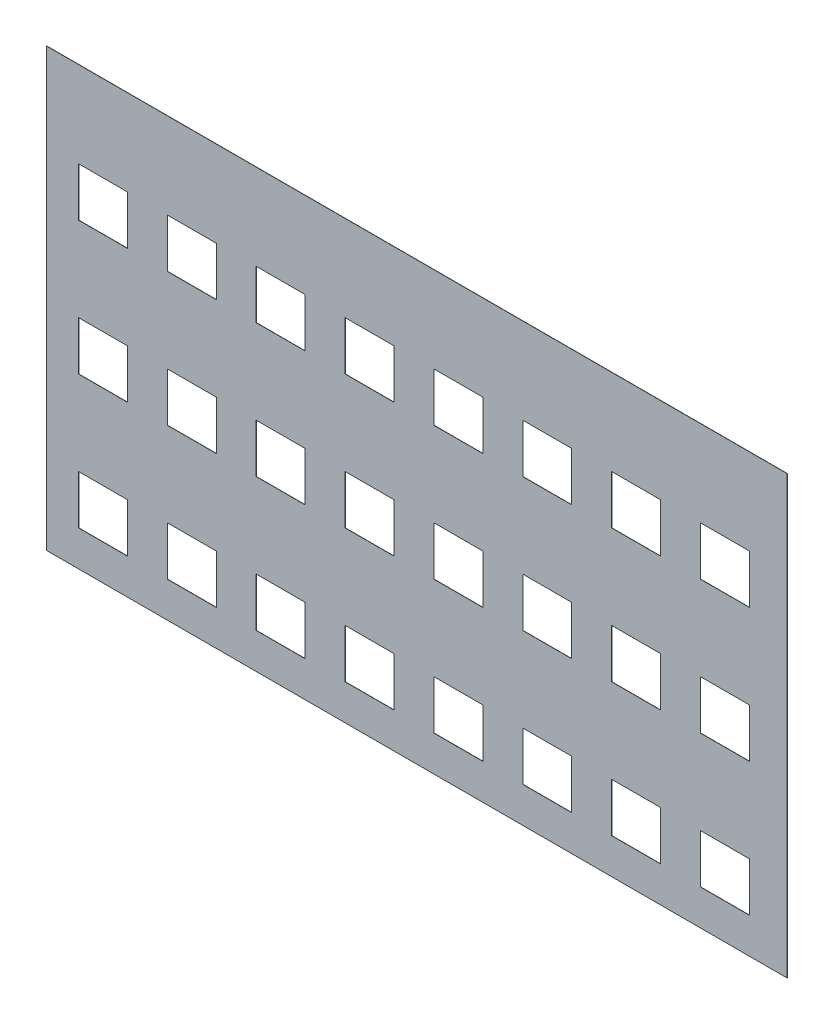
SolidWorks part; units mm, degrees
ref_plane "Front Plane" through (0, 0, 0) normal (0, 0, 1) x (1, 0, 0)
ref_plane "Top Plane" through (0, 0, 0) normal (0, 1, 0) x (1, 0, 0)
ref_plane "Right Plane" through (0, 0, 0) normal (1, 0, 0) x (0, 0, -1)
sketch "Model" plane through (0, 0, 0) normal (0, 0, 1) x (1, 0, 0)
  line L0 (1790, 440) -> (1640, 440)
  line L1 (1640, 440) -> (1640, 595)
  line L2 (1640, 595) -> (1650, 595)
  line L3 (1650, 595) -> (1650, 662)
  line L4 (1650, 662) -> (1780, 662)
  line L5 (1780, 662) -> (1780, 595)
  line L6 (1780, 595) -> (1790, 595)
  line L7 (1790, 595) -> (1790, 440)
  line L8 (1595, 440) -> (1445, 440)
  line L9 (1445, 440) -> (1445, 595)
  line L10 (1445, 595) -> (1455, 595)
  line L11 (1455, 595) -> (1455, 662)
  line L12 (1455, 662) -> (1585, 662)
  line L13 (1585, 662) -> (1585, 595)
  line L14 (1585, 595) -> (1595, 595)
  line L15 (1595, 595) -> (1595, 440)
  line L16 (1400, 440) -> (1250, 440)
  line L17 (1250, 440) -> (1250, 595)
  line L18 (1250, 595) -> (1260, 595)
  line L19 (1260, 595) -> (1260, 662)
  line L20 (1260, 662) -> (1390, 662)
  line L21 (1390, 662) -> (1390, 595)
  line L22 (1390, 595) -> (1400, 595)
  line L23 (1400, 595) -> (1400, 440)
  line L24 (1205, 440) -> (1055, 440)
  line L25 (1055, 440) -> (1055, 595)
  line L26 (1055, 595) -> (1065, 595)
  line L27 (1065, 595) -> (1065, 662)
  line L28 (1065, 662) -> (1195, 662)
  line L29 (1195, 662) -> (1195, 595)
  line L30 (1195, 595) -> (1205, 595)
  line L31 (1205, 595) -> (1205, 440)
  line L32 (1010, 440) -> (860, 440)
  line L33 (860, 440) -> (860, 595)
  line L34 (860, 595) -> (870, 595)
  line L35 (870, 595) -> (870, 662)
  line L36 (870, 662) -> (1000, 662)
  line L37 (1000, 662) -> (1000, 595)
  line L38 (1000, 595) -> (1010, 595)
  line L39 (1010, 595) -> (1010, 440)
  line L40 (815, 440) -> (665, 440)
  line L41 (665, 440) -> (665, 595)
  line L42 (665, 595) -> (675, 595)
  line L43 (675, 595) -> (675, 662)
  line L44 (675, 662) -> (805, 662)
  line L45 (805, 662) -> (805, 595)
  line L46 (805, 595) -> (815, 595)
  line L47 (815, 595) -> (815, 440)
  line L48 (620, 440) -> (470, 440)
  line L49 (470, 440) -> (470, 595)
  line L50 (470, 595) -> (480, 595)
  line L51 (480, 595) -> (480, 662)
  line L52 (480, 662) -> (610, 662)
  line L53 (610, 662) -> (610, 595)
  line L54 (610, 595) -> (620, 595)
  line L55 (620, 595) -> (620, 440)
  line L56 (425, 440) -> (275, 440)
  line L57 (275, 440) -> (275, 595)
  line L58 (275, 595) -> (285, 595)
  line L59 (285, 595) -> (285, 662)
  line L60 (285, 662) -> (415, 662)
  line L61 (415, 662) -> (415, 595)
  line L62 (415, 595) -> (425, 595)
  line L63 (425, 595) -> (425, 440)
  line L64 (230, 440) -> (80, 440)
  line L65 (80, 440) -> (80, 595)
  line L66 (80, 595) -> (90, 595)
  line L67 (90, 595) -> (90, 662)
  line L68 (90, 662) -> (220, 662)
  line L69 (220, 662) -> (220, 595)
  line L70 (220, 595) -> (230, 595)
  line L71 (230, 595) -> (230, 440)
  line L72 (1790, 805) -> (1640, 805)
  line L73 (1640, 805) -> (1640, 960)
  line L74 (1640, 960) -> (1650, 960)
  line L75 (1650, 960) -> (1650, 1027)
  line L76 (1650, 1027) -> (1780, 1027)
  line L77 (1780, 1027) -> (1780, 960)
  line L78 (1780, 960) -> (1790, 960)
  line L79 (1790, 960) -> (1790, 805)
  line L80 (1595, 805) -> (1445, 805)
  line L81 (1445, 805) -> (1445, 960)
  line L82 (1445, 960) -> (1455, 960)
  line L83 (1455, 960) -> (1455, 1027)
  line L84 (1455, 1027) -> (1585, 1027)
  line L85 (1585, 1027) -> (1585, 960)
  line L86 (1585, 960) -> (1595, 960)
  line L87 (1595, 960) -> (1595, 805)
  line L88 (1400, 805) -> (1250, 805)
  line L89 (1250, 805) -> (1250, 960)
  line L90 (1250, 960) -> (1260, 960)
  line L91 (1260, 960) -> (1260, 1027)
  line L92 (1260, 1027) -> (1390, 1027)
  line L93 (1390, 1027) -> (1390, 960)
  line L94 (1390, 960) -> (1400, 960)
  line L95 (1400, 960) -> (1400, 805)
  line L96 (1205, 805) -> (1055, 805)
  line L97 (1055, 805) -> (1055, 960)
  line L98 (1055, 960) -> (1065, 960)
  line L99 (1065, 960) -> (1065, 1027)
  line L100 (1065, 1027) -> (1195, 1027)
  line L101 (1195, 1027) -> (1195, 960)
  line L102 (1195, 960) -> (1205, 960)
  line L103 (1205, 960) -> (1205, 805)
  line L104 (1010, 805) -> (860, 805)
  line L105 (860, 805) -> (860, 960)
  line L106 (860, 960) -> (870, 960)
  line L107 (870, 960) -> (870, 1027)
  line L108 (870, 1027) -> (1000, 1027)
  line L109 (1000, 1027) -> (1000, 960)
  line L110 (1000, 960) -> (1010, 960)
  line L111 (1010, 960) -> (1010, 805)
  line L112 (815, 805) -> (665, 805)
  line L113 (665, 805) -> (665, 960)
  line L114 (665, 960) -> (675, 960)
  line L115 (675, 960) -> (675, 1027)
  line L116 (675, 1027) -> (805, 1027)
  line L117 (805, 1027) -> (805, 960)
  line L118 (805, 960) -> (815, 960)
  line L119 (815, 960) -> (815, 805)
  line L120 (620, 805) -> (470, 805)
  line L121 (470, 805) -> (470, 960)
  line L122 (470, 960) -> (480, 960)
  line L123 (480, 960) -> (480, 1027)
  line L124 (480, 1027) -> (610, 1027)
  line L125 (610, 1027) -> (610, 960)
  line L126 (610, 960) -> (620, 960)
  line L127 (620, 960) -> (620, 805)
  line L128 (425, 805) -> (275, 805)
  line L129 (275, 805) -> (275, 960)
  line L130 (275, 960) -> (285, 960)
  line L131 (285, 960) -> (285, 1027)
  line L132 (285, 1027) -> (415, 1027)
  line L133 (415, 1027) -> (415, 960)
  line L134 (415, 960) -> (425, 960)
  line L135 (425, 960) -> (425, 805)
  line L136 (230, 805) -> (80, 805)
  line L137 (80, 805) -> (80, 960)
  line L138 (80, 960) -> (90, 960)
  line L139 (90, 960) -> (90, 1027)
  line L140 (90, 1027) -> (220, 1027)
  line L141 (220, 1027) -> (220, 960)
  line L142 (220, 960) -> (230, 960)
  line L143 (230, 960) -> (230, 805)
  line L144 (1790, 75) -> (1640, 75)
  line L145 (1640, 75) -> (1640, 230)
  line L146 (1640, 230) -> (1650, 230)
  line L147 (1650, 230) -> (1650, 297)
  line L148 (1650, 297) -> (1780, 297)
  line L149 (1780, 297) -> (1780, 230)
  line L150 (1780, 230) -> (1790, 230)
  line L151 (1790, 230) -> (1790, 75)
  line L152 (1595, 75) -> (1445, 75)
  line L153 (1445, 75) -> (1445, 230)
  line L154 (1445, 230) -> (1455, 230)
  line L155 (1455, 230) -> (1455, 297)
  line L156 (1455, 297) -> (1585, 297)
  line L157 (1585, 297) -> (1585, 230)
  line L158 (1585, 230) -> (1595, 230)
  line L159 (1595, 230) -> (1595, 75)
  line L160 (1400, 75) -> (1250, 75)
  line L161 (1250, 75) -> (1250, 230)
  line L162 (1250, 230) -> (1260, 230)
  line L163 (1260, 230) -> (1260, 297)
  line L164 (1260, 297) -> (1390, 297)
  line L165 (1390, 297) -> (1390, 230)
  line L166 (1390, 230) -> (1400, 230)
  line L167 (1400, 230) -> (1400, 75)
  line L168 (1205, 75) -> (1055, 75)
  line L169 (1055, 75) -> (1055, 230)
  line L170 (1055, 230) -> (1065, 230)
  line L171 (1065, 230) -> (1065, 297)
  line L172 (1065, 297) -> (1195, 297)
  line L173 (1195, 297) -> (1195, 230)
  line L174 (1195, 230) -> (1205, 230)
  line L175 (1205, 230) -> (1205, 75)
  line L176 (1010, 75) -> (860, 75)
  line L177 (860, 75) -> (860, 230)
  line L178 (860, 230) -> (870, 230)
  line L179 (870, 230) -> (870, 297)
  line L180 (870, 297) -> (1000, 297)
  line L181 (1000, 297) -> (1000, 230)
  line L182 (1000, 230) -> (1010, 230)
  line L183 (1010, 230) -> (1010, 75)
  line L184 (815, 75) -> (665, 75)
  line L185 (665, 75) -> (665, 230)
  line L186 (665, 230) -> (675, 230)
  line L187 (675, 230) -> (675, 297)
  line L188 (675, 297) -> (805, 297)
  line L189 (805, 297) -> (805, 230)
  line L190 (805, 230) -> (815, 230)
  line L191 (815, 230) -> (815, 75)
  line L192 (620, 75) -> (470, 75)
  line L193 (470, 75) -> (470, 230)
  line L194 (470, 230) -> (480, 230)
  line L195 (480, 230) -> (480, 297)
  line L196 (480, 297) -> (610, 297)
  line L197 (610, 297) -> (610, 230)
  line L198 (610, 230) -> (620, 230)
  line L199 (620, 230) -> (620, 75)
  line L200 (425, 75) -> (275, 75)
  line L201 (275, 75) -> (275, 230)
  line L202 (275, 230) -> (285, 230)
  line L203 (285, 230) -> (285, 297)
  line L204 (285, 297) -> (415, 297)
  line L205 (415, 297) -> (415, 230)
  line L206 (415, 230) -> (425, 230)
  line L207 (425, 230) -> (425, 75)
  line L208 (230, 75) -> (80, 75)
  line L209 (80, 75) -> (80, 230)
  line L210 (80, 230) -> (90, 230)
  line L211 (90, 230) -> (90, 297)
  line L212 (90, 297) -> (220, 297)
  line L213 (220, 297) -> (220, 230)
  line L214 (220, 230) -> (230, 230)
  line L215 (230, 230) -> (230, 75)
  line L216 (0, 1180) -> (0, 0)
  line L217 (0, 0) -> (1870, 0)
  line L218 (1870, 0) -> (1870, 1180)
  line L219 (1870, 1180) -> (0, 1180)
  dimension "D1" = 3
base flange "Base-Flange1" sketch "Model" thickness 0.6 reverse thickness direction no parameters "D1"=0.7366
sketch "Sketch6" plane through (0, 0, 0) normal (0, 0, 1) x (1, 0, 0)
  line L3 (1705, 805) -> (1725, 805)
  line L7 (1725, 1027) -> (1705, 1027)
  line L8 (1779, 1026) -> (1725, 1026)
  line L9 (1651, 1026) -> (1651, 959)
  line L10 (1651, 959) -> (1641, 959)
  line L11 (1641, 959) -> (1641, 806)
  line L12 (1641, 806) -> (1705, 806)
  line L13 (1789, 806) -> (1789, 959)
  line L14 (1789, 959) -> (1779, 959)
  line L15 (1779, 959) -> (1779, 1026)
  line L16 (1705, 1026) -> (1651, 1026)
  line L17 (1780, 1027) -> (1650, 1027) construction
  line L18 (1705, 1027) -> (1705, 1026)
  line L19 (1725, 1027) -> (1725, 1026)
  line L20 (1705, 806) -> (1705, 805)
  line L21 (1725, 806) -> (1725, 805)
  line L22 (1725, 806) -> (1789, 806)
  line L23 (1641, 806) -> (1789, 806) construction
  line L24 (1779, 1026) -> (1651, 1026) construction
  line L25 (1640, 805) -> (1790, 805) construction
  line L26 (1650, 1027) -> (1650, 960) construction
  line L27 (1650, 960) -> (1640, 960) construction
  line L28 (1640, 960) -> (1640, 805) construction
  line L29 (1790, 805) -> (1790, 960) construction
  line L30 (1790, 960) -> (1780, 960) construction
  line L31 (1780, 960) -> (1780, 1027) construction
  line L32 (1705, 440) -> (1725, 440)
  line L33 (1725, 662) -> (1705, 662)
  line L34 (1779, 661) -> (1725, 661)
  line L35 (1651, 661) -> (1651, 594)
  line L36 (1651, 594) -> (1641, 594)
  line L37 (1641, 594) -> (1641, 441)
  line L38 (1641, 441) -> (1705, 441)
  line L39 (1789, 441) -> (1789, 594)
  line L40 (1789, 594) -> (1779, 594)
  line L41 (1779, 594) -> (1779, 661)
  line L42 (1705, 661) -> (1651, 661)
  line L43 (1705, 662) -> (1705, 661)
  line L44 (1725, 662) -> (1725, 661)
  line L45 (1705, 441) -> (1705, 440)
  line L46 (1725, 441) -> (1725, 440)
  line L47 (1725, 441) -> (1789, 441)
  line L48 (1705, 75) -> (1725, 75)
  line L49 (1725, 297) -> (1705, 297)
  line L50 (1779, 296) -> (1725, 296)
  line L51 (1651, 296) -> (1651, 229)
  line L52 (1651, 229) -> (1641, 229)
  line L53 (1641, 229) -> (1641, 76)
  line L54 (1641, 76) -> (1705, 76)
  line L55 (1789, 76) -> (1789, 229)
  line L56 (1789, 229) -> (1779, 229)
  line L57 (1779, 229) -> (1779, 296)
  line L58 (1705, 296) -> (1651, 296)
  line L59 (1705, 297) -> (1705, 296)
  line L60 (1725, 297) -> (1725, 296)
  line L61 (1705, 76) -> (1705, 75)
  line L62 (1725, 76) -> (1725, 75)
  line L63 (1725, 76) -> (1789, 76)
  dimension "D1" = 1
  dimension "D2" = 3
base flange "Tab1" sketch "Sketch6" thickness 0.6 reverse thickness direction no parameters "D1"=0.7366
sketch "Sketch7" plane through (0, 0, 0) normal (0, 0, 1) x (1, 0, 0)
  line L1 (1870, 1180) -> (1935, 1180)
  line L2 (1870, 1180) -> (1870, 0)
  line L3 (1870, 0) -> (1935, 0)
  line L4 (1935, 1180) -> (1935, 0)
  line L5 (0, 0) -> (-65, 0)
  line L6 (0, 0) -> (0, 1180)
  line L7 (0, 1180) -> (-65, 1180)
  line L8 (-65, 0) -> (-65, 1180)
  dimension "D1" = 65
  dimension "D2" = 65
base flange "Tab2" sketch "Sketch7" thickness 0.6 reverse thickness direction no parameters "D1"=0.7366
sketch "Sketch9" plane through (0, 0, 0) normal (0, 0, 1) x (1, 0, 0)
  line L1 (30.4802, 1078.5447) -> (1870.8092, 1078.5447)
  line L2 (30.4802, 1078.5447) -> (30.4802, 32.6023)
  line L3 (30.4802, 32.6023) -> (1870.8092, 32.6023)
  line L4 (1870.8092, 1078.5447) -> (1870.8092, 32.6023)
extrude "Boss-Extrude1" add sketch "Sketch9" against normal up to surface (0.6 mm away)
sketch "Sketch8" plane through (0, 0, 0) normal (0, 0, 1) x (1, 0, 0)
  line L84 (1701.0507, 947.9116) -> (1701.0507, 815.9116)
  line L85 (1833.0507, 947.9116) -> (1701.0507, 947.9116)
  line L86 (1833.0507, 815.9116) -> (1833.0507, 947.9116)
  line L87 (1701.0507, 815.9116) -> (1833.0507, 815.9116)
  line L288 (1461.0507, 947.9116) -> (1461.0507, 815.9116)
  line L289 (1461.0507, 815.9116) -> (1593.0507, 815.9116)
  line L290 (1593.0507, 815.9116) -> (1593.0507, 947.9116)
  line L291 (1593.0507, 947.9116) -> (1461.0507, 947.9116)
  line L292 (1221.0507, 947.9116) -> (1221.0507, 815.9116)
  line L293 (1221.0507, 815.9116) -> (1353.0507, 815.9116)
  line L294 (1353.0507, 815.9116) -> (1353.0507, 947.9116)
  line L295 (1353.0507, 947.9116) -> (1221.0507, 947.9116)
  line L296 (981.0507, 947.9116) -> (981.0507, 815.9116)
  line L297 (981.0507, 815.9116) -> (1113.0507, 815.9116)
  line L298 (1113.0507, 815.9116) -> (1113.0507, 947.9116)
  line L299 (1113.0507, 947.9116) -> (981.0507, 947.9116)
  line L300 (741.0507, 947.9116) -> (741.0507, 815.9116)
  line L301 (741.0507, 815.9116) -> (873.0507, 815.9116)
  line L302 (873.0507, 815.9116) -> (873.0507, 947.9116)
  line L303 (873.0507, 947.9116) -> (741.0507, 947.9116)
  line L304 (501.0507, 947.9116) -> (501.0507, 815.9116)
  line L305 (501.0507, 815.9116) -> (633.0507, 815.9116)
  line L306 (633.0507, 815.9116) -> (633.0507, 947.9116)
  line L307 (633.0507, 947.9116) -> (501.0507, 947.9116)
  line L308 (261.0507, 947.9116) -> (261.0507, 815.9116)
  line L309 (261.0507, 815.9116) -> (393.0507, 815.9116)
  line L310 (393.0507, 815.9116) -> (393.0507, 947.9116)
  line L311 (393.0507, 947.9116) -> (261.0507, 947.9116)
  line L312 (21.0507, 947.9116) -> (21.0507, 815.9116)
  line L313 (21.0507, 815.9116) -> (153.0507, 815.9116)
  line L314 (153.0507, 815.9116) -> (153.0507, 947.9116)
  line L315 (153.0507, 947.9116) -> (21.0507, 947.9116)
  line L316 (1461.0507, 587.9116) -> (1461.0507, 455.9116)
  line L317 (1461.0507, 455.9116) -> (1593.0507, 455.9116)
  line L318 (1593.0507, 455.9116) -> (1593.0507, 587.9116)
  line L319 (1593.0507, 587.9116) -> (1461.0507, 587.9116)
  line L320 (1221.0507, 587.9116) -> (1221.0507, 455.9116)
  line L321 (1221.0507, 455.9116) -> (1353.0507, 455.9116)
  line L322 (1353.0507, 455.9116) -> (1353.0507, 587.9116)
  line L323 (1353.0507, 587.9116) -> (1221.0507, 587.9116)
  line L324 (981.0507, 587.9116) -> (981.0507, 455.9116)
  line L325 (981.0507, 455.9116) -> (1113.0507, 455.9116)
  line L326 (1113.0507, 455.9116) -> (1113.0507, 587.9116)
  line L327 (1113.0507, 587.9116) -> (981.0507, 587.9116)
  line L328 (741.0507, 587.9116) -> (741.0507, 455.9116)
  line L329 (741.0507, 455.9116) -> (873.0507, 455.9116)
  line L330 (873.0507, 455.9116) -> (873.0507, 587.9116)
  line L331 (873.0507, 587.9116) -> (741.0507, 587.9116)
  line L332 (501.0507, 587.9116) -> (501.0507, 455.9116)
  line L333 (501.0507, 455.9116) -> (633.0507, 455.9116)
  line L334 (633.0507, 455.9116) -> (633.0507, 587.9116)
  line L335 (633.0507, 587.9116) -> (501.0507, 587.9116)
  line L336 (261.0507, 587.9116) -> (261.0507, 455.9116)
  line L337 (261.0507, 455.9116) -> (393.0507, 455.9116)
  line L338 (393.0507, 455.9116) -> (393.0507, 587.9116)
  line L339 (393.0507, 587.9116) -> (261.0507, 587.9116)
  line L340 (21.0507, 587.9116) -> (21.0507, 455.9116)
  line L341 (21.0507, 455.9116) -> (153.0507, 455.9116)
  line L342 (153.0507, 455.9116) -> (153.0507, 587.9116)
  line L343 (153.0507, 587.9116) -> (21.0507, 587.9116)
  line L344 (1461.0507, 227.9116) -> (1461.0507, 95.9116)
  line L345 (1461.0507, 95.9116) -> (1593.0507, 95.9116)
  line L346 (1593.0507, 95.9116) -> (1593.0507, 227.9116)
  line L347 (1593.0507, 227.9116) -> (1461.0507, 227.9116)
  line L348 (1221.0507, 227.9116) -> (1221.0507, 95.9116)
  line L349 (1221.0507, 95.9116) -> (1353.0507, 95.9116)
  line L350 (1353.0507, 95.9116) -> (1353.0507, 227.9116)
  line L351 (1353.0507, 227.9116) -> (1221.0507, 227.9116)
  line L352 (981.0507, 227.9116) -> (981.0507, 95.9116)
  line L353 (981.0507, 95.9116) -> (1113.0507, 95.9116)
  line L354 (1113.0507, 95.9116) -> (1113.0507, 227.9116)
  line L355 (1113.0507, 227.9116) -> (981.0507, 227.9116)
  line L356 (741.0507, 227.9116) -> (741.0507, 95.9116)
  line L357 (741.0507, 95.9116) -> (873.0507, 95.9116)
  line L358 (873.0507, 95.9116) -> (873.0507, 227.9116)
  line L359 (873.0507, 227.9116) -> (741.0507, 227.9116)
  line L360 (501.0507, 227.9116) -> (501.0507, 95.9116)
  line L361 (501.0507, 95.9116) -> (633.0507, 95.9116)
  line L362 (633.0507, 95.9116) -> (633.0507, 227.9116)
  line L363 (633.0507, 227.9116) -> (501.0507, 227.9116)
  line L364 (261.0507, 227.9116) -> (261.0507, 95.9116)
  line L365 (261.0507, 95.9116) -> (393.0507, 95.9116)
  line L366 (393.0507, 95.9116) -> (393.0507, 227.9116)
  line L367 (393.0507, 227.9116) -> (261.0507, 227.9116)
  line L368 (21.0507, 227.9116) -> (21.0507, 95.9116)
  line L369 (21.0507, 95.9116) -> (153.0507, 95.9116)
  line L370 (153.0507, 95.9116) -> (153.0507, 227.9116)
  line L371 (153.0507, 227.9116) -> (21.0507, 227.9116)
  line L372 (1701.0507, 587.9116) -> (1701.0507, 455.9116)
  line L373 (1701.0507, 455.9116) -> (1833.0507, 455.9116)
  line L374 (1833.0507, 455.9116) -> (1833.0507, 587.9116)
  line L375 (1833.0507, 587.9116) -> (1701.0507, 587.9116)
  line L376 (1701.0507, 227.9116) -> (1701.0507, 95.9116)
  line L377 (1701.0507, 95.9116) -> (1833.0507, 95.9116)
  line L378 (1833.0507, 95.9116) -> (1833.0507, 227.9116)
  line L379 (1833.0507, 227.9116) -> (1701.0507, 227.9116)
  dimension "D1" = 3
extrude "Cut-Extrude1" cut sketch "Sketch8" against normal blind 10 normal cut yes
sketch "Bend-Lines1" [suppressed] plane through (0, 0, 0) normal (0, 1, 0) x (1, 0, 0)
sketch "Bounding-Box1" [suppressed] plane through (0, 0, 0) normal (0, 1, 0) x (1, 0, 0)
sheet metal parameters "Sheet-Metal1" thickness 0.6 parameters "D1"=0.7366
flat pattern "Flat-Pattern1" [suppressed]
sketch "Bend-Lines2" plane through (0, 0, 0) normal (0, 1, 0) x (1, 0, 0)
sketch3d "Bounding-Box2" [suppressed]
  line L0 (0, 0, 0) -> (-1870, 0, 0) construction
  line L1 (0, 1180, 0) -> (-1870, 1180, 0) construction
  line L2 (0, 0, 0) -> (0, 1180, 0) construction
  line L3 (-1870, 0, 0) -> (-1870, 1180, 0) construction
sheet metal parameters "Sheet-Metal2" thickness 0.6 parameters "D1"=0.7366
flat pattern "Flat-Pattern2"
sketch "Bend-Lines3" plane through (0, 0, 0) normal (0, 1, 0) x (1, 0, 0)
sketch3d "Bounding-Box3" [suppressed]
  line L0 (0, 0, 0) -> (-1870, 0, 0) construction
  line L1 (0, 1180, 0) -> (-1870, 1180, 0) construction
  line L2 (0, 0, 0) -> (0, 1180, 0) construction
  line L3 (-1870, 0, 0) -> (-1870, 1180, 0) construction
sheet metal parameters "Sheet-Metal5" thickness 0.6 parameters "D1"=0.7366
flat pattern "Flat-Pattern5"
sketch "Bend-Lines4" plane through (0, 0, 0) normal (0, 1, 0) x (1, 0, 0)
sketch3d "Bounding-Box4" [suppressed]
  line L0 (65, 0, 0) -> (-1935, 0, 0) construction
  line L1 (65, 1180, 0) -> (-1935, 1180, 0) construction
  line L2 (65, 0, 0) -> (65, 1180, 0) construction
  line L3 (-1935, 0, 0) -> (-1935, 1180, 0) construction
sheet metal parameters "Sheet-Metal6" thickness 0.6 parameters "D1"=0.7366
flat pattern "Flat-Pattern5" [suppressed]
sketch "Bend-Lines4" plane through (0, 0, 0) normal (0, 1, 0) x (1, 0, 0)
sketch3d "Bounding-Box4" [suppressed]
  line L0 (65, 0, 0) -> (-1935, 0, 0) construction
  line L1 (65, 1180, 0) -> (-1935, 1180, 0) construction
  line L2 (65, 0, 0) -> (65, 1180, 0) construction
  line L3 (-1935, 0, 0) -> (-1935, 1180, 0) construction
sketch "Sketch8-1" plane through (0, 0, 0) normal (0, 0, 1) x (1, 0, 0)
  line L0 (91.0507, 947.9116) -> (91.0507, 815.9116)
  line L1 (223.0507, 947.9116) -> (91.0507, 947.9116)
  line L2 (223.0507, 815.9116) -> (223.0507, 947.9116)
  line L3 (91.0507, 815.9116) -> (223.0507, 815.9116)
  line L4 (67.0507, 1045.9116) -> (82.0507, 1045.9116)
  line L5 (232.0507, 1045.9116) -> (82.0507, 1045.9116)
  line L6 (247.0507, 1045.9116) -> (232.0507, 1045.9116)
  line L7 (247.0507, 968.9116) -> (247.0507, 1045.9116)
  line L8 (247.0507, 793.9116) -> (247.0507, 968.9116)
  line L9 (67.0507, 793.9116) -> (247.0507, 793.9116)
  line L10 (67.0507, 973.9116) -> (67.0507, 793.9116)
  line L11 (67.0507, 973.9116) -> (67.0507, 1045.9116)
  line L12 (321.0507, 947.9116) -> (321.0507, 815.9116)
  line L13 (453.0507, 947.9116) -> (321.0507, 947.9116)
  line L14 (453.0507, 815.9116) -> (453.0507, 947.9116)
  line L15 (321.0507, 815.9116) -> (453.0507, 815.9116)
  line L16 (297.0507, 1045.9116) -> (312.0507, 1045.9116)
  line L17 (462.0507, 1045.9116) -> (312.0507, 1045.9116)
  line L18 (477.0507, 1045.9116) -> (462.0507, 1045.9116)
  line L19 (477.0507, 968.9116) -> (477.0507, 1045.9116)
  line L20 (477.0507, 793.9116) -> (477.0507, 968.9116)
  line L21 (297.0507, 793.9116) -> (477.0507, 793.9116)
  line L22 (297.0507, 973.9116) -> (297.0507, 793.9116)
  line L23 (297.0507, 973.9116) -> (297.0507, 1045.9116)
  line L24 (551.0507, 947.9116) -> (551.0507, 815.9116)
  line L25 (683.0507, 947.9116) -> (551.0507, 947.9116)
  line L26 (683.0507, 815.9116) -> (683.0507, 947.9116)
  line L27 (551.0507, 815.9116) -> (683.0507, 815.9116)
  line L28 (527.0507, 1045.9116) -> (542.0507, 1045.9116)
  line L29 (692.0507, 1045.9116) -> (542.0507, 1045.9116)
  line L30 (707.0507, 1045.9116) -> (692.0507, 1045.9116)
  line L31 (707.0507, 968.9116) -> (707.0507, 1045.9116)
  line L32 (707.0507, 793.9116) -> (707.0507, 968.9116)
  line L33 (527.0507, 793.9116) -> (707.0507, 793.9116)
  line L34 (527.0507, 973.9116) -> (527.0507, 793.9116)
  line L35 (527.0507, 973.9116) -> (527.0507, 1045.9116)
  line L36 (781.0507, 947.9116) -> (781.0507, 815.9116)
  line L37 (913.0507, 947.9116) -> (781.0507, 947.9116)
  line L38 (913.0507, 815.9116) -> (913.0507, 947.9116)
  line L39 (781.0507, 815.9116) -> (913.0507, 815.9116)
  line L40 (757.0507, 1045.9116) -> (772.0507, 1045.9116)
  line L41 (922.0507, 1045.9116) -> (772.0507, 1045.9116)
  line L42 (937.0507, 1045.9116) -> (922.0507, 1045.9116)
  line L43 (937.0507, 968.9116) -> (937.0507, 1045.9116)
  line L44 (937.0507, 793.9116) -> (937.0507, 968.9116)
  line L45 (757.0507, 793.9116) -> (937.0507, 793.9116)
  line L46 (757.0507, 973.9116) -> (757.0507, 793.9116)
  line L47 (757.0507, 973.9116) -> (757.0507, 1045.9116)
  line L48 (1011.0507, 947.9116) -> (1011.0507, 815.9116)
  line L49 (1143.0507, 947.9116) -> (1011.0507, 947.9116)
  line L50 (1143.0507, 815.9116) -> (1143.0507, 947.9116)
  line L51 (1011.0507, 815.9116) -> (1143.0507, 815.9116)
  line L52 (987.0507, 1045.9116) -> (1002.0507, 1045.9116)
  line L53 (1152.0507, 1045.9116) -> (1002.0507, 1045.9116)
  line L54 (1167.0507, 1045.9116) -> (1152.0507, 1045.9116)
  line L55 (1167.0507, 968.9116) -> (1167.0507, 1045.9116)
  line L56 (1167.0507, 793.9116) -> (1167.0507, 968.9116)
  line L57 (987.0507, 793.9116) -> (1167.0507, 793.9116)
  line L58 (987.0507, 973.9116) -> (987.0507, 793.9116)
  line L59 (987.0507, 973.9116) -> (987.0507, 1045.9116)
  line L60 (1241.0507, 947.9116) -> (1241.0507, 815.9116)
  line L61 (1373.0507, 947.9116) -> (1241.0507, 947.9116)
  line L62 (1373.0507, 815.9116) -> (1373.0507, 947.9116)
  line L63 (1241.0507, 815.9116) -> (1373.0507, 815.9116)
  line L64 (1217.0507, 1045.9116) -> (1232.0507, 1045.9116)
  line L65 (1382.0507, 1045.9116) -> (1232.0507, 1045.9116)
  line L66 (1397.0507, 1045.9116) -> (1382.0507, 1045.9116)
  line L67 (1397.0507, 968.9116) -> (1397.0507, 1045.9116)
  line L68 (1397.0507, 793.9116) -> (1397.0507, 968.9116)
  line L69 (1217.0507, 793.9116) -> (1397.0507, 793.9116)
  line L70 (1217.0507, 973.9116) -> (1217.0507, 793.9116)
  line L71 (1217.0507, 973.9116) -> (1217.0507, 1045.9116)
  line L72 (1471.0507, 947.9116) -> (1471.0507, 815.9116)
  line L73 (1603.0507, 947.9116) -> (1471.0507, 947.9116)
  line L74 (1603.0507, 815.9116) -> (1603.0507, 947.9116)
  line L75 (1471.0507, 815.9116) -> (1603.0507, 815.9116)
  line L76 (1447.0507, 1045.9116) -> (1462.0507, 1045.9116)
  line L77 (1612.0507, 1045.9116) -> (1462.0507, 1045.9116)
  line L78 (1627.0507, 1045.9116) -> (1612.0507, 1045.9116)
  line L79 (1627.0507, 968.9116) -> (1627.0507, 1045.9116)
  line L80 (1627.0507, 793.9116) -> (1627.0507, 968.9116)
  line L81 (1447.0507, 793.9116) -> (1627.0507, 793.9116)
  line L82 (1447.0507, 973.9116) -> (1447.0507, 793.9116)
  line L83 (1447.0507, 973.9116) -> (1447.0507, 1045.9116)
  line L84 (1701.0507, 947.9116) -> (1701.0507, 815.9116)
  line L85 (1833.0507, 947.9116) -> (1701.0507, 947.9116)
  line L86 (1833.0507, 815.9116) -> (1833.0507, 947.9116)
  line L87 (1701.0507, 815.9116) -> (1833.0507, 815.9116)
  line L88 (1677.0507, 1045.9116) -> (1692.0507, 1045.9116)
  line L89 (1842.0507, 1045.9116) -> (1692.0507, 1045.9116)
  line L90 (1857.0507, 1045.9116) -> (1842.0507, 1045.9116)
  line L91 (1857.0507, 968.9116) -> (1857.0507, 1045.9116)
  line L92 (1857.0507, 793.9116) -> (1857.0507, 968.9116)
  line L93 (1677.0507, 793.9116) -> (1857.0507, 793.9116)
  line L94 (1677.0507, 973.9116) -> (1677.0507, 793.9116)
  line L95 (1677.0507, 973.9116) -> (1677.0507, 1045.9116)
  line L96 (91.0507, 587.9116) -> (91.0507, 455.9116)
  line L97 (223.0507, 587.9116) -> (91.0507, 587.9116)
  line L98 (223.0507, 455.9116) -> (223.0507, 587.9116)
  line L99 (91.0507, 455.9116) -> (223.0507, 455.9116)
  line L100 (67.0507, 685.9116) -> (82.0507, 685.9116)
  line L101 (232.0507, 685.9116) -> (82.0507, 685.9116)
  line L102 (247.0507, 685.9116) -> (232.0507, 685.9116)
  line L103 (247.0507, 608.9116) -> (247.0507, 685.9116)
  line L104 (247.0507, 433.9116) -> (247.0507, 608.9116)
  line L105 (67.0507, 433.9116) -> (247.0507, 433.9116)
  line L106 (67.0507, 613.9116) -> (67.0507, 433.9116)
  line L107 (67.0507, 613.9116) -> (67.0507, 685.9116)
  line L108 (321.0507, 587.9116) -> (321.0507, 455.9116)
  line L109 (453.0507, 587.9116) -> (321.0507, 587.9116)
  line L110 (453.0507, 455.9116) -> (453.0507, 587.9116)
  line L111 (321.0507, 455.9116) -> (453.0507, 455.9116)
  line L112 (297.0507, 685.9116) -> (312.0507, 685.9116)
  line L113 (462.0507, 685.9116) -> (312.0507, 685.9116)
  line L114 (477.0507, 685.9116) -> (462.0507, 685.9116)
  line L115 (477.0507, 608.9116) -> (477.0507, 685.9116)
  line L116 (477.0507, 433.9116) -> (477.0507, 608.9116)
  line L117 (297.0507, 433.9116) -> (477.0507, 433.9116)
  line L118 (297.0507, 613.9116) -> (297.0507, 433.9116)
  line L119 (297.0507, 613.9116) -> (297.0507, 685.9116)
  line L120 (551.0507, 587.9116) -> (551.0507, 455.9116)
  line L121 (683.0507, 587.9116) -> (551.0507, 587.9116)
  line L122 (683.0507, 455.9116) -> (683.0507, 587.9116)
  line L123 (551.0507, 455.9116) -> (683.0507, 455.9116)
  line L124 (527.0507, 685.9116) -> (542.0507, 685.9116)
  line L125 (692.0507, 685.9116) -> (542.0507, 685.9116)
  line L126 (707.0507, 685.9116) -> (692.0507, 685.9116)
  line L127 (707.0507, 608.9116) -> (707.0507, 685.9116)
  line L128 (707.0507, 433.9116) -> (707.0507, 608.9116)
  line L129 (527.0507, 433.9116) -> (707.0507, 433.9116)
  line L130 (527.0507, 613.9116) -> (527.0507, 433.9116)
  line L131 (527.0507, 613.9116) -> (527.0507, 685.9116)
  line L132 (781.0507, 587.9116) -> (781.0507, 455.9116)
  line L133 (913.0507, 587.9116) -> (781.0507, 587.9116)
  line L134 (913.0507, 455.9116) -> (913.0507, 587.9116)
  line L135 (781.0507, 455.9116) -> (913.0507, 455.9116)
  line L136 (757.0507, 685.9116) -> (772.0507, 685.9116)
  line L137 (922.0507, 685.9116) -> (772.0507, 685.9116)
  line L138 (937.0507, 685.9116) -> (922.0507, 685.9116)
  line L139 (937.0507, 608.9116) -> (937.0507, 685.9116)
  line L140 (937.0507, 433.9116) -> (937.0507, 608.9116)
  line L141 (757.0507, 433.9116) -> (937.0507, 433.9116)
  line L142 (757.0507, 613.9116) -> (757.0507, 433.9116)
  line L143 (757.0507, 613.9116) -> (757.0507, 685.9116)
  line L144 (1011.0507, 587.9116) -> (1011.0507, 455.9116)
  line L145 (1143.0507, 587.9116) -> (1011.0507, 587.9116)
  line L146 (1143.0507, 455.9116) -> (1143.0507, 587.9116)
  line L147 (1011.0507, 455.9116) -> (1143.0507, 455.9116)
  line L148 (987.0507, 685.9116) -> (1002.0507, 685.9116)
  line L149 (1152.0507, 685.9116) -> (1002.0507, 685.9116)
  line L150 (1167.0507, 685.9116) -> (1152.0507, 685.9116)
  line L151 (1167.0507, 608.9116) -> (1167.0507, 685.9116)
  line L152 (1167.0507, 433.9116) -> (1167.0507, 608.9116)
  line L153 (987.0507, 433.9116) -> (1167.0507, 433.9116)
  line L154 (987.0507, 613.9116) -> (987.0507, 433.9116)
  line L155 (987.0507, 613.9116) -> (987.0507, 685.9116)
  line L156 (1241.0507, 587.9116) -> (1241.0507, 455.9116)
  line L157 (1373.0507, 587.9116) -> (1241.0507, 587.9116)
  line L158 (1373.0507, 455.9116) -> (1373.0507, 587.9116)
  line L159 (1241.0507, 455.9116) -> (1373.0507, 455.9116)
  line L160 (1217.0507, 685.9116) -> (1232.0507, 685.9116)
  line L161 (1382.0507, 685.9116) -> (1232.0507, 685.9116)
  line L162 (1397.0507, 685.9116) -> (1382.0507, 685.9116)
  line L163 (1397.0507, 608.9116) -> (1397.0507, 685.9116)
  line L164 (1397.0507, 433.9116) -> (1397.0507, 608.9116)
  line L165 (1217.0507, 433.9116) -> (1397.0507, 433.9116)
  line L166 (1217.0507, 613.9116) -> (1217.0507, 433.9116)
  line L167 (1217.0507, 613.9116) -> (1217.0507, 685.9116)
  line L168 (1471.0507, 587.9116) -> (1471.0507, 455.9116)
  line L169 (1603.0507, 587.9116) -> (1471.0507, 587.9116)
  line L170 (1603.0507, 455.9116) -> (1603.0507, 587.9116)
  line L171 (1471.0507, 455.9116) -> (1603.0507, 455.9116)
  line L172 (1447.0507, 685.9116) -> (1462.0507, 685.9116)
  line L173 (1612.0507, 685.9116) -> (1462.0507, 685.9116)
  line L174 (1627.0507, 685.9116) -> (1612.0507, 685.9116)
  line L175 (1627.0507, 608.9116) -> (1627.0507, 685.9116)
  line L176 (1627.0507, 433.9116) -> (1627.0507, 608.9116)
  line L177 (1447.0507, 433.9116) -> (1627.0507, 433.9116)
  line L178 (1447.0507, 613.9116) -> (1447.0507, 433.9116)
  line L179 (1447.0507, 613.9116) -> (1447.0507, 685.9116)
  line L180 (1701.0507, 587.9116) -> (1701.0507, 455.9116)
  line L181 (1833.0507, 587.9116) -> (1701.0507, 587.9116)
  line L182 (1833.0507, 455.9116) -> (1833.0507, 587.9116)
  line L183 (1701.0507, 455.9116) -> (1833.0507, 455.9116)
  line L184 (1677.0507, 685.9116) -> (1692.0507, 685.9116)
  line L185 (1842.0507, 685.9116) -> (1692.0507, 685.9116)
  line L186 (1857.0507, 685.9116) -> (1842.0507, 685.9116)
  line L187 (1857.0507, 608.9116) -> (1857.0507, 685.9116)
  line L188 (1857.0507, 433.9116) -> (1857.0507, 608.9116)
  line L189 (1677.0507, 433.9116) -> (1857.0507, 433.9116)
  line L190 (1677.0507, 613.9116) -> (1677.0507, 433.9116)
  line L191 (1677.0507, 613.9116) -> (1677.0507, 685.9116)
  line L192 (91.0507, 227.9116) -> (91.0507, 95.9116)
  line L193 (223.0507, 227.9116) -> (91.0507, 227.9116)
  line L194 (223.0507, 95.9116) -> (223.0507, 227.9116)
  line L195 (91.0507, 95.9116) -> (223.0507, 95.9116)
  line L196 (67.0507, 325.9116) -> (82.0507, 325.9116)
  line L197 (232.0507, 325.9116) -> (82.0507, 325.9116)
  line L198 (247.0507, 325.9116) -> (232.0507, 325.9116)
  line L199 (247.0507, 248.9116) -> (247.0507, 325.9116)
  line L200 (247.0507, 73.9116) -> (247.0507, 248.9116)
  line L201 (67.0507, 73.9116) -> (247.0507, 73.9116)
  line L202 (67.0507, 253.9116) -> (67.0507, 73.9116)
  line L203 (67.0507, 253.9116) -> (67.0507, 325.9116)
  line L204 (321.0507, 227.9116) -> (321.0507, 95.9116)
  line L205 (453.0507, 227.9116) -> (321.0507, 227.9116)
  line L206 (453.0507, 95.9116) -> (453.0507, 227.9116)
  line L207 (321.0507, 95.9116) -> (453.0507, 95.9116)
  line L208 (297.0507, 325.9116) -> (312.0507, 325.9116)
  line L209 (462.0507, 325.9116) -> (312.0507, 325.9116)
  line L210 (477.0507, 325.9116) -> (462.0507, 325.9116)
  line L211 (477.0507, 248.9116) -> (477.0507, 325.9116)
  line L212 (477.0507, 73.9116) -> (477.0507, 248.9116)
  line L213 (297.0507, 73.9116) -> (477.0507, 73.9116)
  line L214 (297.0507, 253.9116) -> (297.0507, 73.9116)
  line L215 (297.0507, 253.9116) -> (297.0507, 325.9116)
  line L216 (551.0507, 227.9116) -> (551.0507, 95.9116)
  line L217 (683.0507, 227.9116) -> (551.0507, 227.9116)
  line L218 (683.0507, 95.9116) -> (683.0507, 227.9116)
  line L219 (551.0507, 95.9116) -> (683.0507, 95.9116)
  line L220 (527.0507, 325.9116) -> (542.0507, 325.9116)
  line L221 (692.0507, 325.9116) -> (542.0507, 325.9116)
  line L222 (707.0507, 325.9116) -> (692.0507, 325.9116)
  line L223 (707.0507, 248.9116) -> (707.0507, 325.9116)
  line L224 (707.0507, 73.9116) -> (707.0507, 248.9116)
  line L225 (527.0507, 73.9116) -> (707.0507, 73.9116)
  line L226 (527.0507, 253.9116) -> (527.0507, 73.9116)
  line L227 (527.0507, 253.9116) -> (527.0507, 325.9116)
  line L228 (781.0507, 227.9116) -> (781.0507, 95.9116)
  line L229 (913.0507, 227.9116) -> (781.0507, 227.9116)
  line L230 (913.0507, 95.9116) -> (913.0507, 227.9116)
  line L231 (781.0507, 95.9116) -> (913.0507, 95.9116)
  line L232 (757.0507, 325.9116) -> (772.0507, 325.9116)
  line L233 (922.0507, 325.9116) -> (772.0507, 325.9116)
  line L234 (937.0507, 325.9116) -> (922.0507, 325.9116)
  line L235 (937.0507, 248.9116) -> (937.0507, 325.9116)
  line L236 (937.0507, 73.9116) -> (937.0507, 248.9116)
  line L237 (757.0507, 73.9116) -> (937.0507, 73.9116)
  line L238 (757.0507, 253.9116) -> (757.0507, 73.9116)
  line L239 (757.0507, 253.9116) -> (757.0507, 325.9116)
  line L240 (1011.0507, 227.9116) -> (1011.0507, 95.9116)
  line L241 (1143.0507, 227.9116) -> (1011.0507, 227.9116)
  line L242 (1143.0507, 95.9116) -> (1143.0507, 227.9116)
  line L243 (1011.0507, 95.9116) -> (1143.0507, 95.9116)
  line L244 (987.0507, 325.9116) -> (1002.0507, 325.9116)
  line L245 (1152.0507, 325.9116) -> (1002.0507, 325.9116)
  line L246 (1167.0507, 325.9116) -> (1152.0507, 325.9116)
  line L247 (1167.0507, 248.9116) -> (1167.0507, 325.9116)
  line L248 (1167.0507, 73.9116) -> (1167.0507, 248.9116)
  line L249 (987.0507, 73.9116) -> (1167.0507, 73.9116)
  line L250 (987.0507, 253.9116) -> (987.0507, 73.9116)
  line L251 (987.0507, 253.9116) -> (987.0507, 325.9116)
  line L252 (1241.0507, 227.9116) -> (1241.0507, 95.9116)
  line L253 (1373.0507, 227.9116) -> (1241.0507, 227.9116)
  line L254 (1373.0507, 95.9116) -> (1373.0507, 227.9116)
  line L255 (1241.0507, 95.9116) -> (1373.0507, 95.9116)
  line L256 (1217.0507, 325.9116) -> (1232.0507, 325.9116)
  line L257 (1382.0507, 325.9116) -> (1232.0507, 325.9116)
  line L258 (1397.0507, 325.9116) -> (1382.0507, 325.9116)
  line L259 (1397.0507, 248.9116) -> (1397.0507, 325.9116)
  line L260 (1397.0507, 73.9116) -> (1397.0507, 248.9116)
  line L261 (1217.0507, 73.9116) -> (1397.0507, 73.9116)
  line L262 (1217.0507, 253.9116) -> (1217.0507, 73.9116)
  line L263 (1217.0507, 253.9116) -> (1217.0507, 325.9116)
  line L264 (1471.0507, 227.9116) -> (1471.0507, 95.9116)
  line L265 (1603.0507, 227.9116) -> (1471.0507, 227.9116)
  line L266 (1603.0507, 95.9116) -> (1603.0507, 227.9116)
  line L267 (1471.0507, 95.9116) -> (1603.0507, 95.9116)
  line L268 (1447.0507, 325.9116) -> (1462.0507, 325.9116)
  line L269 (1612.0507, 325.9116) -> (1462.0507, 325.9116)
  line L270 (1627.0507, 325.9116) -> (1612.0507, 325.9116)
  line L271 (1627.0507, 248.9116) -> (1627.0507, 325.9116)
  line L272 (1627.0507, 73.9116) -> (1627.0507, 248.9116)
  line L273 (1447.0507, 73.9116) -> (1627.0507, 73.9116)
  line L274 (1447.0507, 253.9116) -> (1447.0507, 73.9116)
  line L275 (1447.0507, 253.9116) -> (1447.0507, 325.9116)
  line L276 (1701.0507, 227.9116) -> (1701.0507, 95.9116)
  line L277 (1833.0507, 227.9116) -> (1701.0507, 227.9116)
  line L278 (1833.0507, 95.9116) -> (1833.0507, 227.9116)
  line L279 (1701.0507, 95.9116) -> (1833.0507, 95.9116)
  line L280 (1677.0507, 325.9116) -> (1692.0507, 325.9116)
  line L281 (1842.0507, 325.9116) -> (1692.0507, 325.9116)
  line L282 (1857.0507, 325.9116) -> (1842.0507, 325.9116)
  line L283 (1857.0507, 248.9116) -> (1857.0507, 325.9116)
  line L284 (1857.0507, 73.9116) -> (1857.0507, 248.9116)
  line L285 (1677.0507, 73.9116) -> (1857.0507, 73.9116)
  line L286 (1677.0507, 253.9116) -> (1677.0507, 73.9116)
  line L287 (1677.0507, 253.9116) -> (1677.0507, 325.9116)
  circle A0 centre (242.0507, 881.4116) radius 1.6
  circle A1 centre (72.0507, 886.4116) radius 1.6
  circle A2 centre (242.0507, 1040.9116) radius 1.6
  circle A3 centre (157.0507, 798.9116) radius 1.6
  circle A4 centre (72.0507, 798.9116) radius 1.6
  circle A5 centre (242.0507, 798.9116) radius 1.6
  circle A6 centre (87.0507, 1040.9116) radius 1.6
  circle A7 centre (472.0507, 881.4116) radius 1.6
  circle A8 centre (302.0507, 886.4116) radius 1.6
  circle A9 centre (472.0507, 1040.9116) radius 1.6
  circle A10 centre (387.0507, 798.9116) radius 1.6
  circle A11 centre (302.0507, 798.9116) radius 1.6
  circle A12 centre (472.0507, 798.9116) radius 1.6
  circle A13 centre (317.0507, 1040.9116) radius 1.6
  circle A14 centre (702.0507, 881.4116) radius 1.6
  circle A15 centre (532.0507, 886.4116) radius 1.6
  circle A16 centre (702.0507, 1040.9116) radius 1.6
  circle A17 centre (617.0507, 798.9116) radius 1.6
  circle A18 centre (532.0507, 798.9116) radius 1.6
  circle A19 centre (702.0507, 798.9116) radius 1.6
  circle A20 centre (547.0507, 1040.9116) radius 1.6
  circle A21 centre (932.0507, 881.4116) radius 1.6
  circle A22 centre (762.0507, 886.4116) radius 1.6
  circle A23 centre (932.0507, 1040.9116) radius 1.6
  circle A24 centre (847.0507, 798.9116) radius 1.6
  circle A25 centre (762.0507, 798.9116) radius 1.6
  circle A26 centre (932.0507, 798.9116) radius 1.6
  circle A27 centre (777.0507, 1040.9116) radius 1.6
  circle A28 centre (1162.0507, 881.4116) radius 1.6
  circle A29 centre (992.0507, 886.4116) radius 1.6
  circle A30 centre (1162.0507, 1040.9116) radius 1.6
  circle A31 centre (1077.0507, 798.9116) radius 1.6
  circle A32 centre (992.0507, 798.9116) radius 1.6
  circle A33 centre (1162.0507, 798.9116) radius 1.6
  circle A34 centre (1007.0507, 1040.9116) radius 1.6
  circle A35 centre (1392.0507, 881.4116) radius 1.6
  circle A36 centre (1222.0507, 886.4116) radius 1.6
  circle A37 centre (1392.0507, 1040.9116) radius 1.6
  circle A38 centre (1307.0507, 798.9116) radius 1.6
  circle A39 centre (1222.0507, 798.9116) radius 1.6
  circle A40 centre (1392.0507, 798.9116) radius 1.6
  circle A41 centre (1237.0507, 1040.9116) radius 1.6
  circle A42 centre (1622.0507, 881.4116) radius 1.6
  circle A43 centre (1452.0507, 886.4116) radius 1.6
  circle A44 centre (1622.0507, 1040.9116) radius 1.6
  circle A45 centre (1537.0507, 798.9116) radius 1.6
  circle A46 centre (1452.0507, 798.9116) radius 1.6
  circle A47 centre (1622.0507, 798.9116) radius 1.6
  circle A48 centre (1467.0507, 1040.9116) radius 1.6
  circle A49 centre (1852.0507, 881.4116) radius 1.6
  circle A50 centre (1682.0507, 886.4116) radius 1.6
  circle A51 centre (1852.0507, 1040.9116) radius 1.6
  circle A52 centre (1767.0507, 798.9116) radius 1.6
  circle A53 centre (1682.0507, 798.9116) radius 1.6
  circle A54 centre (1852.0507, 798.9116) radius 1.6
  circle A55 centre (1697.0507, 1040.9116) radius 1.6
  circle A56 centre (242.0507, 521.4116) radius 1.6
  circle A57 centre (72.0507, 526.4116) radius 1.6
  circle A58 centre (242.0507, 680.9116) radius 1.6
  circle A59 centre (157.0507, 438.9116) radius 1.6
  circle A60 centre (72.0507, 438.9116) radius 1.6
  circle A61 centre (242.0507, 438.9116) radius 1.6
  circle A62 centre (87.0507, 680.9116) radius 1.6
  circle A63 centre (472.0507, 521.4116) radius 1.6
  circle A64 centre (302.0507, 526.4116) radius 1.6
  circle A65 centre (472.0507, 680.9116) radius 1.6
  circle A66 centre (387.0507, 438.9116) radius 1.6
  circle A67 centre (302.0507, 438.9116) radius 1.6
  circle A68 centre (472.0507, 438.9116) radius 1.6
  circle A69 centre (317.0507, 680.9116) radius 1.6
  circle A70 centre (702.0507, 521.4116) radius 1.6
  circle A71 centre (532.0507, 526.4116) radius 1.6
  circle A72 centre (702.0507, 680.9116) radius 1.6
  circle A73 centre (617.0507, 438.9116) radius 1.6
  circle A74 centre (532.0507, 438.9116) radius 1.6
  circle A75 centre (702.0507, 438.9116) radius 1.6
  circle A76 centre (547.0507, 680.9116) radius 1.6
  circle A77 centre (932.0507, 521.4116) radius 1.6
  circle A78 centre (762.0507, 526.4116) radius 1.6
  circle A79 centre (932.0507, 680.9116) radius 1.6
  circle A80 centre (847.0507, 438.9116) radius 1.6
  circle A81 centre (762.0507, 438.9116) radius 1.6
  circle A82 centre (932.0507, 438.9116) radius 1.6
  circle A83 centre (777.0507, 680.9116) radius 1.6
  circle A84 centre (1162.0507, 521.4116) radius 1.6
  circle A85 centre (992.0507, 526.4116) radius 1.6
  circle A86 centre (1162.0507, 680.9116) radius 1.6
  circle A87 centre (1077.0507, 438.9116) radius 1.6
  circle A88 centre (992.0507, 438.9116) radius 1.6
  circle A89 centre (1162.0507, 438.9116) radius 1.6
  circle A90 centre (1007.0507, 680.9116) radius 1.6
  circle A91 centre (1392.0507, 521.4116) radius 1.6
  circle A92 centre (1222.0507, 526.4116) radius 1.6
  circle A93 centre (1392.0507, 680.9116) radius 1.6
  circle A94 centre (1307.0507, 438.9116) radius 1.6
  circle A95 centre (1222.0507, 438.9116) radius 1.6
  circle A96 centre (1392.0507, 438.9116) radius 1.6
  circle A97 centre (1237.0507, 680.9116) radius 1.6
  circle A98 centre (1622.0507, 521.4116) radius 1.6
  circle A99 centre (1452.0507, 526.4116) radius 1.6
  circle A100 centre (1622.0507, 680.9116) radius 1.6
  circle A101 centre (1537.0507, 438.9116) radius 1.6
  circle A102 centre (1452.0507, 438.9116) radius 1.6
  circle A103 centre (1622.0507, 438.9116) radius 1.6
  circle A104 centre (1467.0507, 680.9116) radius 1.6
  circle A105 centre (1852.0507, 521.4116) radius 1.6
  circle A106 centre (1682.0507, 526.4116) radius 1.6
  circle A107 centre (1852.0507, 680.9116) radius 1.6
  circle A108 centre (1767.0507, 438.9116) radius 1.6
  circle A109 centre (1682.0507, 438.9116) radius 1.6
  circle A110 centre (1852.0507, 438.9116) radius 1.6
  circle A111 centre (1697.0507, 680.9116) radius 1.6
  circle A112 centre (242.0507, 161.4116) radius 1.6
  circle A113 centre (72.0507, 166.4116) radius 1.6
  circle A114 centre (242.0507, 320.9116) radius 1.6
  circle A115 centre (157.0507, 78.9116) radius 1.6
  circle A116 centre (72.0507, 78.9116) radius 1.6
  circle A117 centre (242.0507, 78.9116) radius 1.6
  circle A118 centre (87.0507, 320.9116) radius 1.6
  circle A119 centre (472.0507, 161.4116) radius 1.6
  circle A120 centre (302.0507, 166.4116) radius 1.6
  circle A121 centre (472.0507, 320.9116) radius 1.6
  circle A122 centre (387.0507, 78.9116) radius 1.6
  circle A123 centre (302.0507, 78.9116) radius 1.6
  circle A124 centre (472.0507, 78.9116) radius 1.6
  circle A125 centre (317.0507, 320.9116) radius 1.6
  circle A126 centre (702.0507, 161.4116) radius 1.6
  circle A127 centre (532.0507, 166.4116) radius 1.6
  circle A128 centre (702.0507, 320.9116) radius 1.6
  circle A129 centre (617.0507, 78.9116) radius 1.6
  circle A130 centre (532.0507, 78.9116) radius 1.6
  circle A131 centre (702.0507, 78.9116) radius 1.6
  circle A132 centre (547.0507, 320.9116) radius 1.6
  circle A133 centre (932.0507, 161.4116) radius 1.6
  circle A134 centre (762.0507, 166.4116) radius 1.6
  circle A135 centre (932.0507, 320.9116) radius 1.6
  circle A136 centre (847.0507, 78.9116) radius 1.6
  circle A137 centre (762.0507, 78.9116) radius 1.6
  circle A138 centre (932.0507, 78.9116) radius 1.6
  circle A139 centre (777.0507, 320.9116) radius 1.6
  circle A140 centre (1162.0507, 161.4116) radius 1.6
  circle A141 centre (992.0507, 166.4116) radius 1.6
  circle A142 centre (1162.0507, 320.9116) radius 1.6
  circle A143 centre (1077.0507, 78.9116) radius 1.6
  circle A144 centre (992.0507, 78.9116) radius 1.6
  circle A145 centre (1162.0507, 78.9116) radius 1.6
  circle A146 centre (1007.0507, 320.9116) radius 1.6
  circle A147 centre (1392.0507, 161.4116) radius 1.6
  circle A148 centre (1222.0507, 166.4116) radius 1.6
  circle A149 centre (1392.0507, 320.9116) radius 1.6
  circle A150 centre (1307.0507, 78.9116) radius 1.6
  circle A151 centre (1222.0507, 78.9116) radius 1.6
  circle A152 centre (1392.0507, 78.9116) radius 1.6
  circle A153 centre (1237.0507, 320.9116) radius 1.6
  circle A154 centre (1622.0507, 161.4116) radius 1.6
  circle A155 centre (1452.0507, 166.4116) radius 1.6
  circle A156 centre (1622.0507, 320.9116) radius 1.6
  circle A157 centre (1537.0507, 78.9116) radius 1.6
  circle A158 centre (1452.0507, 78.9116) radius 1.6
  circle A159 centre (1622.0507, 78.9116) radius 1.6
  circle A160 centre (1467.0507, 320.9116) radius 1.6
  circle A161 centre (1852.0507, 161.4116) radius 1.6
  circle A162 centre (1682.0507, 166.4116) radius 1.6
  circle A163 centre (1852.0507, 320.9116) radius 1.6
  circle A164 centre (1767.0507, 78.9116) radius 1.6
  circle A165 centre (1682.0507, 78.9116) radius 1.6
  circle A166 centre (1852.0507, 78.9116) radius 1.6
  circle A167 centre (1697.0507, 320.9116) radius 1.6
  dimension "D1" = 3.2
  dimension "D2" = 8
  dimension "D3" = 3
sheet metal parameters "Sheet-Metal7" thickness 0.6 parameters "D1"=0.7366
flat pattern "Flat-Pattern5" [suppressed]
sketch "Bend-Lines4" plane through (0, 0, 0) normal (0, 1, 0) x (1, 0, 0)
sketch3d "Bounding-Box4" [suppressed]
  line L0 (65, 0, 0) -> (-1935, 0, 0) construction
  line L1 (65, 1180, 0) -> (-1935, 1180, 0) construction
  line L2 (65, 0, 0) -> (65, 1180, 0) construction
  line L3 (-1935, 0, 0) -> (-1935, 1180, 0) construction
sketch "Sketch8-1" [suppressed] plane through (0, 0, 0) normal (0, 0, 1) x (1, 0, 0)
  line L84 (1701.0507, 947.9116) -> (1701.0507, 815.9116)
  line L85 (1833.0507, 947.9116) -> (1701.0507, 947.9116)
  line L86 (1833.0507, 815.9116) -> (1833.0507, 947.9116)
  line L87 (1701.0507, 815.9116) -> (1833.0507, 815.9116)
  line L288 (1461.0507, 947.9116) -> (1461.0507, 815.9116)
  line L289 (1461.0507, 815.9116) -> (1593.0507, 815.9116)
  line L290 (1593.0507, 815.9116) -> (1593.0507, 947.9116)
  line L291 (1593.0507, 947.9116) -> (1461.0507, 947.9116)
  line L292 (1221.0507, 947.9116) -> (1221.0507, 815.9116)
  line L293 (1221.0507, 815.9116) -> (1353.0507, 815.9116)
  line L294 (1353.0507, 815.9116) -> (1353.0507, 947.9116)
  line L295 (1353.0507, 947.9116) -> (1221.0507, 947.9116)
  line L296 (981.0507, 947.9116) -> (981.0507, 815.9116)
  line L297 (981.0507, 815.9116) -> (1113.0507, 815.9116)
  line L298 (1113.0507, 815.9116) -> (1113.0507, 947.9116)
  line L299 (1113.0507, 947.9116) -> (981.0507, 947.9116)
  line L300 (741.0507, 947.9116) -> (741.0507, 815.9116)
  line L301 (741.0507, 815.9116) -> (873.0507, 815.9116)
  line L302 (873.0507, 815.9116) -> (873.0507, 947.9116)
  line L303 (873.0507, 947.9116) -> (741.0507, 947.9116)
  line L304 (501.0507, 947.9116) -> (501.0507, 815.9116)
  line L305 (501.0507, 815.9116) -> (633.0507, 815.9116)
  line L306 (633.0507, 815.9116) -> (633.0507, 947.9116)
  line L307 (633.0507, 947.9116) -> (501.0507, 947.9116)
  line L308 (261.0507, 947.9116) -> (261.0507, 815.9116)
  line L309 (261.0507, 815.9116) -> (393.0507, 815.9116)
  line L310 (393.0507, 815.9116) -> (393.0507, 947.9116)
  line L311 (393.0507, 947.9116) -> (261.0507, 947.9116)
  line L312 (21.0507, 947.9116) -> (21.0507, 815.9116)
  line L313 (21.0507, 815.9116) -> (153.0507, 815.9116)
  line L314 (153.0507, 815.9116) -> (153.0507, 947.9116)
  line L315 (153.0507, 947.9116) -> (21.0507, 947.9116)
  line L316 (1461.0507, 587.9116) -> (1461.0507, 455.9116)
  line L317 (1461.0507, 455.9116) -> (1593.0507, 455.9116)
  line L318 (1593.0507, 455.9116) -> (1593.0507, 587.9116)
  line L319 (1593.0507, 587.9116) -> (1461.0507, 587.9116)
  line L320 (1221.0507, 587.9116) -> (1221.0507, 455.9116)
  line L321 (1221.0507, 455.9116) -> (1353.0507, 455.9116)
  line L322 (1353.0507, 455.9116) -> (1353.0507, 587.9116)
  line L323 (1353.0507, 587.9116) -> (1221.0507, 587.9116)
  line L324 (981.0507, 587.9116) -> (981.0507, 455.9116)
  line L325 (981.0507, 455.9116) -> (1113.0507, 455.9116)
  line L326 (1113.0507, 455.9116) -> (1113.0507, 587.9116)
  line L327 (1113.0507, 587.9116) -> (981.0507, 587.9116)
  line L328 (741.0507, 587.9116) -> (741.0507, 455.9116)
  line L329 (741.0507, 455.9116) -> (873.0507, 455.9116)
  line L330 (873.0507, 455.9116) -> (873.0507, 587.9116)
  line L331 (873.0507, 587.9116) -> (741.0507, 587.9116)
  line L332 (501.0507, 587.9116) -> (501.0507, 455.9116)
  line L333 (501.0507, 455.9116) -> (633.0507, 455.9116)
  line L334 (633.0507, 455.9116) -> (633.0507, 587.9116)
  line L335 (633.0507, 587.9116) -> (501.0507, 587.9116)
  line L336 (261.0507, 587.9116) -> (261.0507, 455.9116)
  line L337 (261.0507, 455.9116) -> (393.0507, 455.9116)
  line L338 (393.0507, 455.9116) -> (393.0507, 587.9116)
  line L339 (393.0507, 587.9116) -> (261.0507, 587.9116)
  line L340 (21.0507, 587.9116) -> (21.0507, 455.9116)
  line L341 (21.0507, 455.9116) -> (153.0507, 455.9116)
  line L342 (153.0507, 455.9116) -> (153.0507, 587.9116)
  line L343 (153.0507, 587.9116) -> (21.0507, 587.9116)
  line L344 (1461.0507, 227.9116) -> (1461.0507, 95.9116)
  line L345 (1461.0507, 95.9116) -> (1593.0507, 95.9116)
  line L346 (1593.0507, 95.9116) -> (1593.0507, 227.9116)
  line L347 (1593.0507, 227.9116) -> (1461.0507, 227.9116)
  line L348 (1221.0507, 227.9116) -> (1221.0507, 95.9116)
  line L349 (1221.0507, 95.9116) -> (1353.0507, 95.9116)
  line L350 (1353.0507, 95.9116) -> (1353.0507, 227.9116)
  line L351 (1353.0507, 227.9116) -> (1221.0507, 227.9116)
  line L352 (981.0507, 227.9116) -> (981.0507, 95.9116)
  line L353 (981.0507, 95.9116) -> (1113.0507, 95.9116)
  line L354 (1113.0507, 95.9116) -> (1113.0507, 227.9116)
  line L355 (1113.0507, 227.9116) -> (981.0507, 227.9116)
  line L356 (741.0507, 227.9116) -> (741.0507, 95.9116)
  line L357 (741.0507, 95.9116) -> (873.0507, 95.9116)
  line L358 (873.0507, 95.9116) -> (873.0507, 227.9116)
  line L359 (873.0507, 227.9116) -> (741.0507, 227.9116)
  line L360 (501.0507, 227.9116) -> (501.0507, 95.9116)
  line L361 (501.0507, 95.9116) -> (633.0507, 95.9116)
  line L362 (633.0507, 95.9116) -> (633.0507, 227.9116)
  line L363 (633.0507, 227.9116) -> (501.0507, 227.9116)
  line L364 (261.0507, 227.9116) -> (261.0507, 95.9116)
  line L365 (261.0507, 95.9116) -> (393.0507, 95.9116)
  line L366 (393.0507, 95.9116) -> (393.0507, 227.9116)
  line L367 (393.0507, 227.9116) -> (261.0507, 227.9116)
  line L368 (21.0507, 227.9116) -> (21.0507, 95.9116)
  line L369 (21.0507, 95.9116) -> (153.0507, 95.9116)
  line L370 (153.0507, 95.9116) -> (153.0507, 227.9116)
  line L371 (153.0507, 227.9116) -> (21.0507, 227.9116)
  line L372 (1701.0507, 587.9116) -> (1701.0507, 455.9116)
  line L373 (1701.0507, 455.9116) -> (1833.0507, 455.9116)
  line L374 (1833.0507, 455.9116) -> (1833.0507, 587.9116)
  line L375 (1833.0507, 587.9116) -> (1701.0507, 587.9116)
  line L376 (1701.0507, 227.9116) -> (1701.0507, 95.9116)
  line L377 (1701.0507, 95.9116) -> (1833.0507, 95.9116)
  line L378 (1833.0507, 95.9116) -> (1833.0507, 227.9116)
  line L379 (1833.0507, 227.9116) -> (1701.0507, 227.9116)
  dimension "D1" = 3
